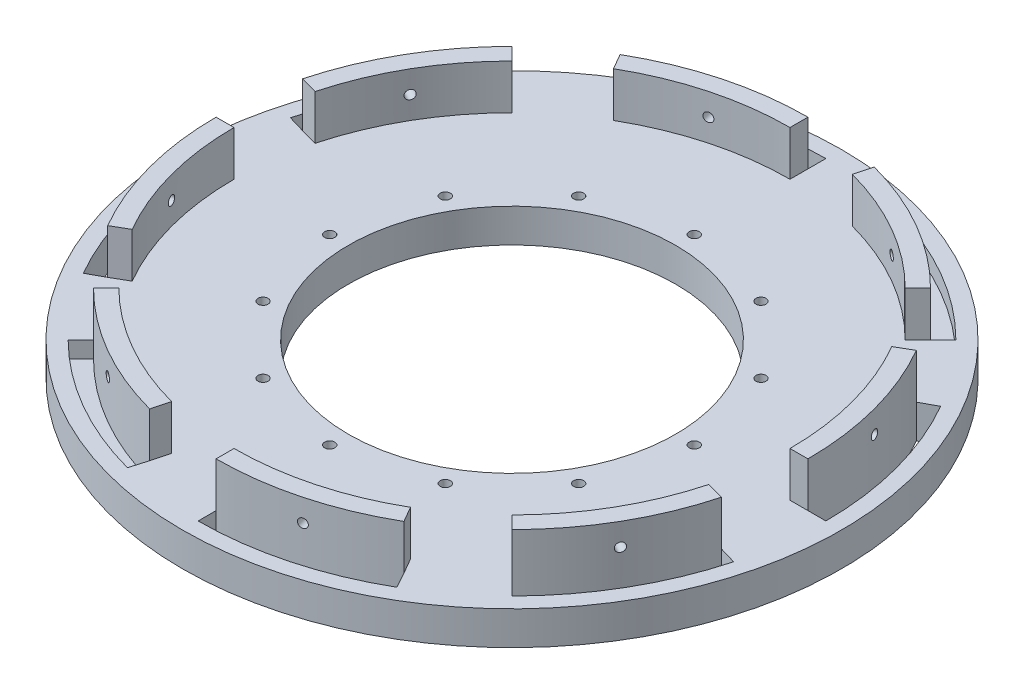
SolidWorks part; units mm, degrees
material "6061-T6 (SS)"
ref_plane "Front Plane" through (0, 0, 0) normal (0, 0, 1) x (1, 0, 0)
ref_plane "Top Plane" through (0, 0, 0) normal (0, 1, 0) x (1, 0, 0)
ref_plane "Right Plane" through (0, 0, 0) normal (1, 0, 0) x (0, 0, -1)
sketch "Sketch1" plane through (0, 0, 0) normal (0, 1, 0) x (1, 0, 0)
  line L5 (0, 0) -> (127.635, 0)
  line L6 (0, 0) -> (0, 127.635)
  line L7 (0, 127.635) -> (127.635, 127.635)
  line L8 (127.635, 0) -> (127.635, 127.635)
  dimension "D1" = 127.635
  dimension "D2" = 127.635
extrude "Boss-Extrude1" add sketch "Sketch1" along normal blind 9.525 contours L5 L8 L7 L6
sketch "Sketch12" plane through (0, 0, 0) normal (0, -1, 0) x (1, 0, 0)
  line L0 (63.8175, 0) -> (63.8175, -127.635) construction
  line L1 (0, 0) -> (127.635, 0) construction
  line L2 (0, -127.635) -> (127.635, -127.635) construction
  line L3 (0, -63.8175) -> (127.635, -63.8175) construction
  line L4 (0, 0) -> (0, -127.635) construction
  line L5 (127.635, 0) -> (127.635, -127.635) construction
  circle A0 centre (63.8175, -63.8175) radius 93.345
  dimension "D1" = 186.69
extrude "Boss-Extrude2" add sketch "Sketch12" against normal up to surface (9.525 mm away) contours A0 up to face at (63.8175, 9.525, -63.8175)
sketch "Sketch5" plane through (0, 9.525, 0) normal (0, 1, 0) x (1, 0, 0)
  circle A0 centre (63.8175, 63.8175) radius 46.355
  circle A3 centre (63.8175, 63.8175) radius 93.345 construction
  dimension "D1" = 92.71
extrude "Cut-Extrude1" cut sketch "Sketch5" against normal blind 9.525
sketch "Sketch11" plane through (0, 9.525, 0) normal (0, 1, 0) x (1, 0, 0)
  line L0 (63.8175, 63.8175) -> (63.8175, 115.443) construction
  circle A0 centre (63.8175, 115.443) radius 1.4351
  dimension "D2" = 2.8702
  dimension "D1" = 51.6255
extrude "Cut-Extrude3" cut sketch "Sketch11" against normal through all contours A0
pattern_circular "CirPattern1" count 12 over 360 about axis through (63.8175, 9.525, -63.8175) along (0, 1, 0) of "Cut-Extrude3"
sketch "Sketch14" plane through (0, 9.525, 0) normal (0, -1, 0) x (1, 0, 0)
  line L0 (63.8175, -63.8175) -> (147.6375, -63.8175) construction
  line L1 (0, -5.2388) -> (0, 5.2388) construction
  line L2 (147.6375, -63.8175) -> (152.7175, -63.8175)
  line L3 (136.3808, -105.7742) -> (140.8401, -108.2104)
  circle A0 centre (63.8175, -63.8175) radius 46.355 construction
  arc A2 (147.6375, -63.8175) -> (136.3808, -105.7742) centre (63.8175, -63.8175) cw
  arc A3 (152.7175, -63.8175) -> (140.8401, -108.2104) centre (63.8175, -63.8175) cw
  point P0 (63.8175, -63.8175)
  point P5 (0, 0)
  point P9 (134.6566, -63.8175)
  point P10 (0, 0)
  point P12 (0, 0)
  point P15 (0, 0)
  point P16 (0, 0)
  point P17 (0, 0)
  point P18 (0, 0)
  dimension "D1" = 83.82
  dimension "D2" = 88.9
  dimension "D3" = 46.482
  dimension "D4" = 43.942
extrude "Bottom support hole" cut sketch "Sketch14" along normal through all
sketch "Sketch15" plane through (0, 9.525, 0) normal (0, -1, 0) x (1, 0, 0)
  line L0 (63.8175, -63.8175) -> (147.6375, -63.8175) construction
  line L2 (142.5575, -63.8175) -> (147.6375, -63.8175)
  line L3 (131.983, -103.2314) -> (136.3808, -105.7742)
  arc A2 (142.5575, -63.8175) -> (131.983, -103.2314) centre (63.8175, -63.8175) cw
  arc A3 (147.6375, -63.8175) -> (136.3808, -105.7742) centre (63.8175, -63.8175) cw
  point P3 (0, 0)
  point P5 (12.5649, -3.3741)
  point P6 (0, 0)
  point P7 (0, 0)
  point P9 (147.2215, -67.1916)
  point P10 (12.5649, -3.3741)
  point P12 (0, 0)
  point P17 (0, 0)
  point P18 (136.3616, -105.8077)
  point P19 (0, 0)
  point P20 (0, 0)
  dimension "D1" = 43.942
  dimension "D3" = 78.74
extrude "Bottom support guide" add sketch "Sketch15" against normal blind 12.7
ref_plane "Bottom support bolt hole plane" through (153.6961, 0, -41.2358) normal (0.9658, 0, -0.2591) x (-0.2591, 0, -0.9658)
sketch "Sketch16" plane through (153.6961, 0, -41.2358) normal (0.9658, 0, -0.2591) x (-0.2591, 0, -0.9658)
  circle A0 centre (45.1039, 15.875) radius 1.27
  point P2 (0, 0)
  point P4 (88.5379, 28.575)
  point P5 (-66.8209, -12.7)
  dimension "D1" = 2.54
  dimension "D2" = 21.717
  dimension "D3" = 6.35
extrude "Bottom support bolt hole" cut sketch "Sketch16" against normal blind 12.7 and the other way blind 12.7
sketch "Sketch25" plane through (0, 9.525, 0) normal (0, -1, 0) x (1, 0, 0)
  line L0 (63.8175, -63.8175) -> (123.0872, -4.5478) construction
  line L2 (123.0872, -4.5478) -> (126.6793, -0.9557)
  line L3 (144.7953, -42.1754) -> (149.6712, -40.7448)
  line L5 (63.8175, -63.8175) -> (147.6375, -63.8175) construction
  arc A2 (123.0872, -4.5478) -> (144.7953, -42.1754) centre (63.8175, -63.8175) cw
  arc A3 (126.6793, -0.9557) -> (149.6712, -40.7448) centre (63.8175, -63.8175) cw
  point P0 (63.8175, -63.8175)
  point P1 (60.8225, 2.882)
  point P2 (0, 0)
  point P3 (0, 0)
  point P5 (-16.5659, 83.3966)
  point P6 (0, 0)
  point P7 (63.8175, -63.8175)
  point P9 (118.0907, 19.5791)
  point P10 (-16.5659, 83.3966)
  point P12 (0, 0)
  point P15 (0, 0)
  point P16 (37.5692, 41.9471)
  point P19 (60.9886, -28.1606)
  point P20 (0, 0)
  point P21 (52.0446, -29.8725)
  dimension "D1" = 83.82
  dimension "D2" = 88.9
  dimension "D3" = 46.482
  dimension "D4" = 43.942
  dimension "D5" = 45
extrude "Top support hole" cut sketch "Sketch25" along normal blind 4.7625
sketch "Sketch27" plane through (-7.9384, 9.525, 69.1212) normal (0, -1, 0) x (1, 0, 0)
  line L0 (134.6177, -70.0769) -> (131.0256, -73.669) construction
  line L2 (131.0256, -73.669) -> (127.4335, -77.2611)
  line L3 (152.7338, -111.2966) -> (147.826, -112.6083)
  arc A2 (131.0256, -73.669) -> (152.7338, -111.2966) centre (71.7559, -132.9387) cw
  arc A3 (127.4335, -77.2611) -> (147.826, -112.6083) centre (71.7559, -132.9387) cw
  point P0 (168.15, -117.468)
  point P1 (0, 0)
  point P3 (0, 0)
  point P5 (12.5649, -3.3741)
  point P6 (0, 0)
  point P7 (0, 0)
  point P9 (147.2215, -67.1916)
  point P10 (12.5649, -3.3741)
  point P12 (0, 0)
  point P17 (0, 0)
  point P18 (136.3616, -105.8077)
  point P19 (0, 0)
  point P20 (0, 0)
  dimension "D1" = 78.74
extrude "Top support guide" add sketch "Sketch27" against normal blind 12.7
ref_plane "Top support bolt hole plane" through (90.3812, 0, 52.1428) normal (-0.8662, 0, -0.4997) x (-0.4997, 0, 0.8662)
sketch "Sketch29" plane through (90.3812, 0, 52.1428) normal (-0.8662, 0, -0.4997) x (-0.4997, 0, 0.8662)
  line L0 (-108.8891, 22.225) -> (-108.8891, 9.525) construction
  circle A0 centre (-87.1721, 15.875) radius 1.27
  point P2 (0, 0)
  point P4 (85.9025, -1.8609)
  point P5 (-66.8209, -12.7)
  dimension "D1" = 2.54
  dimension "D2" = 21.717
  dimension "D3" = 6.35
extrude "Top support bolt hole" cut sketch "Sketch29" against normal blind 12.7 and the other way blind 12.7
pattern_circular "CirPattern4" count 4 over 360 about axis through (63.8175, 0, -63.8175) along (0, -1, 0) of "Top support bolt hole", "Top support guide", "Top support hole", "Bottom support bolt hole", "Bottom support guide", "Bottom support hole"
